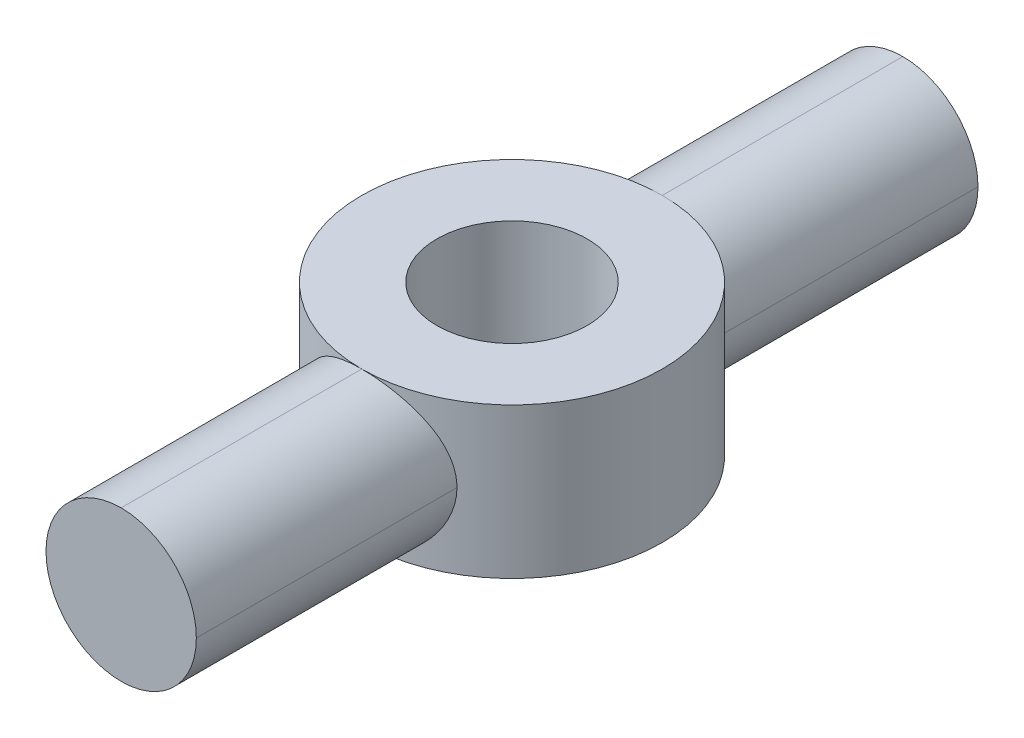
SolidWorks part; units mm, degrees
ref_plane "Plano frontal" through (0, 0, 0) normal (0, 0, 1) x (1, 0, 0)
ref_plane "Plano superior" through (0, 0, 0) normal (0, 1, 0) x (1, 0, 0)
ref_plane "Plano direito" through (0, 0, 0) normal (1, 0, 0) x (0, 0, -1)
sketch "Esboço1" plane through (0, 0, 0) normal (0, 1, 0) x (1, 0, 0)
  line L0 (-12.5, -21.6506) -> (-12.5, -65)
  line L1 (-12.5, 65) -> (12.5, 65)
  line L2 (-12.5, 65) -> (-12.5, 21.6506)
  line L3 (-12.5, -65) -> (12.5, -65)
  line L4 (12.5, 65) -> (12.5, 21.6506)
  line L5 (12.5, -21.6506) -> (12.5, -65)
  arc A0 (-12.5, 21.6506) -> (-12.5, -21.6506) centre (0, 0) ccw
  circle A1 centre (0, 0) radius 12.5
  arc A2 (12.5, -21.6506) -> (12.5, 21.6506) centre (0, 0) ccw
  dimension "D1" = 50
  dimension "D2" = 25
  dimension "D3" = 25
  dimension "D4" = 65
  dimension "D5" = 130
extrude "Ressalto-extrusão1" add sketch "Esboço1" along normal blind 25
fillet "Filete1" radius 12.5 8 edges at (-12.5, 0, -43.3253) (12.5, 0, -43.3253) (-12.5, 25, -43.3253) (12.5, 25, -43.3253) (-12.5, 0, 43.3253) (12.5, 0, 43.3253) (12.5, 25, 43.3253) (-12.5, 25, 43.3253)
